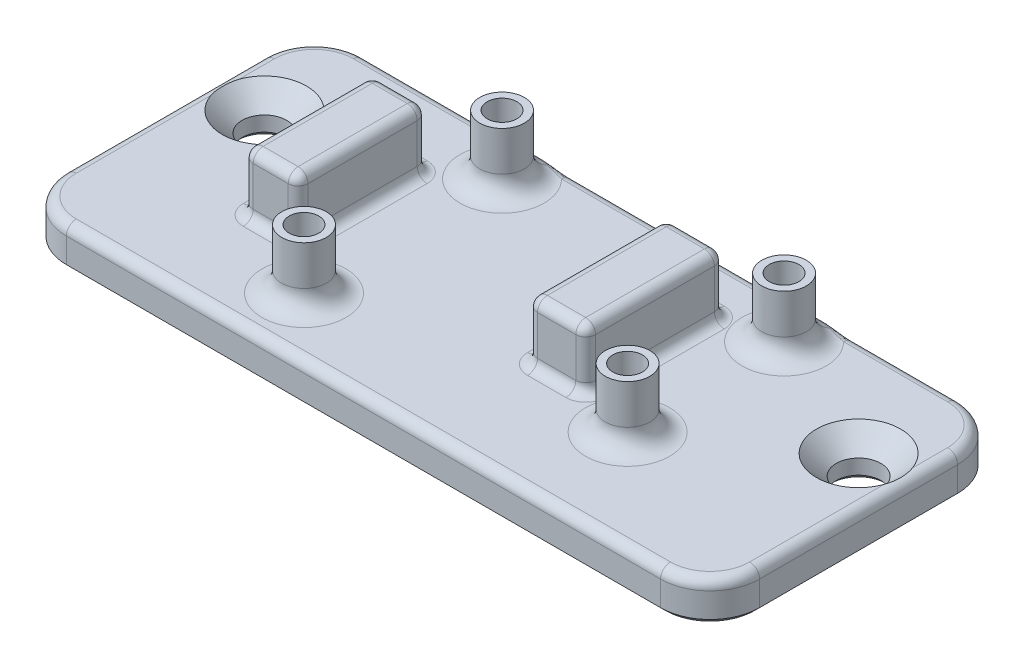
SolidWorks part; units mm, degrees
ref_plane "Спереди" through (0, 0, 0) normal (0, 0, 1) x (1, 0, 0)
ref_plane "Сверху" through (0, 0, 0) normal (0, 1, 0) x (1, 0, 0)
ref_plane "Справа" through (0, 0, 0) normal (1, 0, 0) x (0, 0, -1)
sketch "Эскиз1" plane through (0, 0, 0) normal (0, 1, 0) x (1, 0, 0)
  line L0 (30, 5) -> (-49.2125, 5) construction
  line L1 (-35, -15) -> (35, -15)
  line L2 (-35, -15) -> (-35, 15)
  line L3 (-35, 15) -> (35, 15)
  line L4 (35, -15) -> (35, 15)
  line L5 (0, 15) -> (0, -15) construction
  line L6 (-35, 0) -> (35, 0) construction
  circle A0 centre (-30, 5) radius 2.25
  circle A1 centre (30, 5) radius 2.25
  point P0 (0, 0)
  point P8 (-50, -10)
  dimension "D3" = 60
  dimension "D4" = 4.5
  dimension "D6" = 20
  dimension "D1" = 70
  dimension "D2" = 30
  dimension "D5" = 5
extrude "Бобышка-Вытянуть1" add sketch "Эскиз1" along normal blind 4
fillet "Скругление1" radius 5 4 edges at (-35, 2, -15) (-35, 2, 15) (35, 2, -15) (35, 2, 15)
chamfer "Фаска1" distance 0.5 angle 45 10 edges at (30, 0, -7.25) (-33.5355, 0, 13.5355) (0, 0, 15) (33.5355, 0, 13.5355) (35, 0, 0) (33.5355, 0, -13.5355) (0, 0, -15) (-33.5355, 0, -13.5355) (-35, 0, 0) (-30, 0, -2.75)
sketch "Эскиз2" plane through (0, 4, 0) normal (0, 1, 0) x (1, 0, 0)
  line L0 (16.4744, 11) -> (16.4744, -19.0588) construction
  line L1 (33.5056, 11) -> (-54.0115, 11) construction
  line L2 (30, 15) -> (-30, 15) construction
  line L3 (-12.0046, 18.4995) -> (-12.0046, -17.5301) construction
  line L4 (11.3405, -3.9) -> (11.3405, 10.0929)
  line L5 (11.3405, -3.9) -> (5.4744, -3.9)
  line L6 (5.4744, -3.9) -> (5.4744, 10.1)
  line L7 (11.3405, 10.0929) -> (5.4744, 10.1)
  line L8 (5.4744, 3.1) -> (11.3405, 3.0965) construction
  line L9 (8.4075, -3.9) -> (8.4075, 10.0965) construction
  line L16 (-16.3781, 7.8076) -> (-21.9141, 7.8076)
  line L17 (-16.3781, 7.8076) -> (-16.3781, -5.2198)
  line L18 (-16.3781, -5.2198) -> (-21.9141, -5.2198)
  line L19 (-21.9141, 7.8076) -> (-21.9141, -5.2198)
  line L20 (-19.1461, -5.2198) -> (-19.1461, 7.8076) construction
  line L21 (-16.3781, 1.2939) -> (-21.9141, 1.2939) construction
  circle A0 centre (16.4744, 11) radius 2.25
  circle A1 centre (16.4744, -4.8) radius 2.25
  circle A2 centre (16.4744, -4.8) radius 1.5
  circle A3 centre (16.4744, 11) radius 1.5
  circle A4 centre (-12.0046, 11) radius 1.5
  circle A5 centre (-12.0046, 11) radius 2.25
  circle A6 centre (-12.0046, -9) radius 2.25
  circle A7 centre (-12.0046, -9) radius 1.5
  point P4 (-18.1135, -9)
  point P12 (8.4075, 3.0982)
  point P18 (-25.466, 8.944)
  point P19 (-23.4127, 1.1729)
  point P20 (-25.5842, 5.9121)
  point P21 (-22.8162, 7.6867)
  point P22 (11.3405, 3.0982)
  point P31 (-19.1461, 1.2939)
  dimension "D1" = 4.5
  dimension "D2" = 4
  dimension "D3" = 3
  dimension "D4" = 15.8
  dimension "D5" = 11
  dimension "D6" = 14
  dimension "D7" = 0.9
  dimension "D10" = 20
extrude "Бобышка-Вытянуть2" add sketch "Эскиз2" along normal blind 6
chamfer "Фаска2" distance 2 angle 45 2 edges at (30, 4, -7.25) (-30, 4, -2.75)
sketch "Эскиз3" plane through (0, 10, 0) normal (0, 1, 0) x (1, 0, 0)
  circle A0 centre (16.4744, -4.8) radius 1.5
  circle A1 centre (16.4744, 11) radius 1.5
  circle A2 centre (16.4744, 11) radius 1.5 construction
  circle A3 centre (16.4744, -4.8) radius 1.5 construction
extrude "Вырез-Вытянуть1" cut sketch "Эскиз3" against normal blind 8
fillet "Скругление2" radius 2 4 edges at (-12.0046, 4, 6.75) (-12.0046, 4, -13.25) (16.4744, 4, -13.25) (16.4744, 4, 2.55)
fillet "Скругление3" radius 1 24 edges at (-21.9141, 4, -1.2939) (-16.3781, 4, -1.2939) (5.4744, 4, -3.1) (11.3405, 4, -3.0965) (-16.3781, 7, -7.8076) (-21.9141, 7, -7.8076) (-19.1461, 4, -7.8076) (11.3405, 7, -10.0929) (5.4744, 7, -10.1) (8.4075, 4, -10.0965) (-21.9141, 7, 5.2198) (-16.3781, 7, 5.2198) (-19.1461, 4, 5.2198) (5.4744, 7, 3.9) (11.3405, 7, 3.9) (8.4075, 4, 3.9) (11.3405, 10, -3.0965) (8.4075, 10, 3.9) (5.4744, 10, -3.1) (8.4075, 10, -10.0965) (-19.1461, 10, -7.8076) (-16.3781, 10, -1.2939) (-19.1461, 10, 5.2198) (-21.9141, 10, -1.2939)
fillet "Скругление4" radius 1 12 edges at (-33.5355, 4, -13.5355) (-21.7204, 4, -15) (-12.0046, 4, -15) (2.2349, 4, -15) (16.4744, 4, -15) (23.9553, 4, -15) (33.5355, 4, -13.5355) (35, 4, 0) (33.5355, 4, 13.5355) (0, 4, 15) (-33.5355, 4, 13.5355) (-35, 4, 0)
